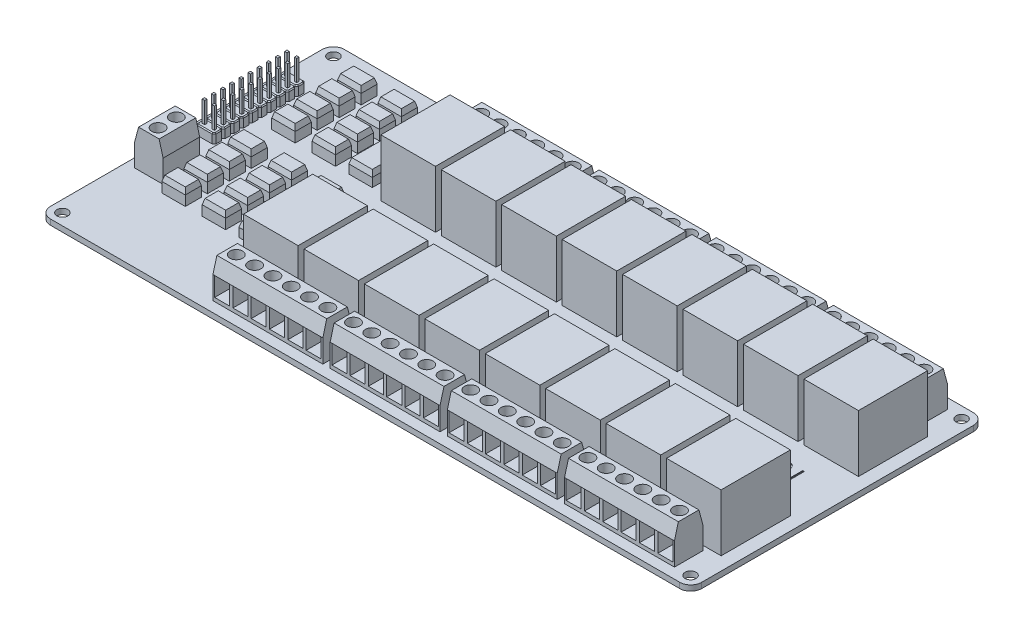
SolidWorks part; units mm, degrees
material "1060 Alloy"
ref_plane "Front" through (0, 0, 0) normal (0, 0, 1) x (1, 0, 0)
ref_plane "Top" through (0, 0, 0) normal (0, 1, 0) x (1, 0, 0)
ref_plane "Right" through (0, 0, 0) normal (1, 0, 0) x (0, 0, -1)
sketch "Sketch1" plane through (0, 0, 0) normal (0, 1, 0) x (1, 0, 0)
  line L1 (-88.9, 40.1) -> (88.9, 40.1)
  line L2 (-88.9, 40.1) -> (-88.9, -40.1)
  line L3 (-88.9, -40.1) -> (88.9, -40.1)
  line L4 (88.9, 40.1) -> (88.9, -40.1)
  line L5 (0, -40.1) -> (0, 40.1) construction
  line L6 (-88.9, 0) -> (88.9, 0) construction
  point P0 (0, 0)
  dimension "D1" = 80.2
  dimension "D2" = 177.8
extrude "Boss-Extrude1" add sketch "Sketch1" along normal blind 1.5
sketch "Sketch2" plane through (0, 1.5, 0) normal (0, 1, 0) x (1, 0, 0)
  line L0 (88.9, -40.1) -> (88.9, 40.1) construction
  line L1 (-85.75, 37) -> (85.75, 37) construction
  line L2 (-85.75, 37) -> (-85.75, -37) construction
  line L3 (-85.75, -37) -> (85.75, -37) construction
  line L4 (85.75, 37) -> (85.75, -37) construction
  line L5 (0, -37) -> (0, 37) construction
  line L6 (-85.75, 0) -> (85.75, 0) construction
  line L7 (88.9, 40.1) -> (-88.9, 40.1) construction
  circle A0 centre (85.75, 37) radius 1.5
  circle A1 centre (85.75, -37) radius 1.5
  circle A2 centre (-85.75, -37) radius 1.5
  circle A3 centre (-85.75, 37) radius 1.5
  point P0 (0, 0)
  point P8 (87.25, 37)
  point P9 (85.75, 38.5)
  dimension "D1" = 3
  dimension "D2" = 1.65
  dimension "D3" = 1.6
  dimension "D4" = 74
  dimension "D5" = 171.5
extrude "Cut-Extrude1" cut sketch "Sketch2" against normal blind 1.5
sketch "Sketch3" plane through (0, 1.5, 0) normal (0, 1, 0) x (1, 0, 0)
  line L0 (88.9, 40.1) -> (-88.9, 40.1) construction
  line L1 (-86.05, 24.7) -> (-81.05, 24.7)
  line L2 (-86.05, 24.7) -> (-86.05, 22.2)
  line L3 (-86.05, 22.2) -> (-81.05, 22.2)
  line L4 (-81.05, 24.7) -> (-81.05, 22.2)
  line L5 (-88.9, 40.1) -> (-88.9, -40.1) construction
  dimension "D1" = 5
  dimension "D2" = 2.5
  dimension "D3" = 15.4
  dimension "D4" = 2.85
extrude "Boss-Extrude2" add sketch "Sketch3" along normal blind 2.6 separate body
sketch "Sketch4" plane through (0, 4.1, 0) normal (0, 1, 0) x (1, 0, 0)
  line L0 (-83.55, 24.7) -> (-83.55, 22.2) construction
  line L1 (-81.05, 24.7) -> (-86.05, 24.7) construction
  line L2 (-86.05, 22.2) -> (-81.05, 22.2) construction
  line L3 (-83.55, 23.45) -> (-82.225, 23.45) construction
  line L4 (-83.55, 23.45) -> (-84.875, 23.45) construction
  line L6 (-82.55, 23.775) -> (-81.9, 23.775)
  line L7 (-82.55, 23.775) -> (-82.55, 23.125)
  line L8 (-82.55, 23.125) -> (-81.9, 23.125)
  line L9 (-81.9, 23.775) -> (-81.9, 23.125)
  line L10 (-82.225, 23.125) -> (-82.225, 23.775) construction
  line L11 (-82.55, 23.45) -> (-81.9, 23.45) construction
  line L12 (-85.2, 23.775) -> (-84.55, 23.775)
  line L13 (-85.2, 23.775) -> (-85.2, 23.125)
  line L14 (-85.2, 23.125) -> (-84.55, 23.125)
  line L15 (-84.55, 23.775) -> (-84.55, 23.125)
  line L16 (-84.875, 23.125) -> (-84.875, 23.775) construction
  line L17 (-85.2, 23.45) -> (-84.55, 23.45) construction
  dimension "D1" = 0.65
  dimension "D2" = 2
  dimension "D3" = 2.65
extrude "Boss-Extrude3" add sketch "Sketch4" along normal blind 5.75 and the other way blind 1.5 separate body
sketch "Sketch5" plane through (-84.55, 0, 0) normal (1, 0, 0) x (0, 0, -1)
  line L0 (23.125, 2.6) -> (23.125, 9.85) construction
  line L1 (23.775, 2.6) -> (23.125, 2.6)
  line L2 (23.775, 2.6) -> (23.775, 3.25)
  line L3 (23.775, 3.25) -> (23.125, 3.25)
  line L4 (23.125, 2.6) -> (23.125, 3.25)
extrude "Boss-Extrude4" add sketch "Sketch5" along normal blind 2
chamfer "Chamfer1" distance 0.5 angle 45 4 edges at (-81.05, 2.8, -24.7) (-81.05, 2.8, -22.2) (-86.05, 2.8, -24.7) (-86.05, 2.8, -22.2)
chamfer "Chamfer2" distance 0.25 angle 45 8 edges at (-81.3, 4.1, -22.45) (-83.55, 4.1, -22.2) (-85.8, 4.1, -22.45) (-86.05, 4.1, -23.45) (-85.8, 4.1, -24.45) (-83.55, 4.1, -24.7) (-81.3, 4.1, -24.45) (-81.05, 4.1, -23.45)
pattern_linear "LPattern1" count 10 spacing 2.5 along (0, 0, 1) of bodies 103 106
sketch "Sketch7" plane through (0, 1.5, 0) normal (0, 1, 0) x (1, 0, 0)
  line L0 (88.9, 40.1) -> (-88.9, 40.1) construction
  line L1 (-76.85, 33.65) -> (-70.45, 33.65)
  line L2 (-76.85, 33.65) -> (-76.85, 29.25)
  line L3 (-76.85, 29.25) -> (-70.45, 29.25)
  line L4 (-70.45, 33.65) -> (-70.45, 29.25)
  line L5 (-88.9, 40.1) -> (-88.9, -40.1) construction
  dimension "D1" = 6.4
  dimension "D2" = 4.4
  dimension "D3" = 6.45
  dimension "D4" = 12.05
extrude "Boss-Extrude6" add sketch "Sketch7" along normal blind 4.23 separate body
chamfer "Chamfer3" distance 1.5 angle 15 4 edges at (-73.65, 5.73, -33.65) (-70.45, 5.73, -31.45) (-73.65, 5.73, -29.25) (-76.85, 5.73, -31.45) first distance on face at (-73.65, 3.615, -33.65) first distance on face at (-70.45, 3.615, -31.45) first distance on face at (-73.65, 3.615, -29.25) first distance on face at (-76.85, 3.615, -31.45)
pattern_linear "LPattern2" count 4 spacing 6 along (0, 0, 1) of bodies 128
pattern_linear "LPattern3" count 2 spacing 30 along (0, 0, 1) count 2 spacing 11 along (1, 0, 0) of bodies 131 130 129 128
sketch "Sketch8" plane through (0, 1.5, 0) normal (0, 1, 0) x (1, 0, 0)
  line L0 (-70.45, 33.65) -> (-76.85, 33.65) construction
  line L1 (-55.8, 33.65) -> (-49.4, 33.65)
  line L2 (-55.8, 33.65) -> (-55.8, 11.25)
  line L3 (-55.8, 11.25) -> (-49.4, 11.25)
  line L4 (-49.4, 33.65) -> (-49.4, 11.25)
  line L5 (-55.8, 3.65) -> (-49.4, 3.65)
  line L6 (-55.8, 3.65) -> (-55.8, -18.75)
  line L7 (-55.8, -18.75) -> (-49.4, -18.75)
  line L8 (-49.4, 3.65) -> (-49.4, -18.75)
  line L9 (-76.85, 11.25) -> (-70.45, 11.25) construction
  line L10 (-59.45, 33.65) -> (-59.45, 29.25) construction
  line L11 (-70.45, 3.65) -> (-76.85, 3.65) construction
  dimension "D1" = 3.65
extrude "Boss-Extrude7" add sketch "Sketch8" along normal blind 3.9 separate body
chamfer "Chamfer4" distance 1.5 angle 15 4 edges at (-52.6, 5.4, -33.65) (-49.4, 5.4, -22.45) (-52.6, 5.4, -11.25) (-55.8, 5.4, -22.45) first distance on face at (-52.6, 3.45, -33.65) first distance on face at (-49.4, 3.45, -22.45) first distance on face at (-52.6, 3.45, -11.25) first distance on face at (-55.8, 3.45, -22.45)
chamfer "Chamfer5" distance 1.5 angle 15 4 edges at (-52.6, 5.4, -3.65) (-49.4, 5.4, 7.55) (-52.6, 5.4, 18.75) (-55.8, 5.4, 7.55) first distance on face at (-52.6, 3.45, -3.65) first distance on face at (-49.4, 3.45, 7.55) first distance on face at (-52.6, 3.45, 18.75) first distance on face at (-55.8, 3.45, 7.55)
sketch "Sketch9" plane through (0, 1.5, 0) normal (0, 1, 0) x (1, 0, 0)
  line L0 (-88.9, 40.1) -> (-88.9, -40.1) construction
  line L1 (-45.1, 28.2) -> (-30.2, 28.2)
  line L2 (-45.1, 28.2) -> (-45.1, 9.3)
  line L3 (-45.1, 9.3) -> (-30.2, 9.3)
  line L4 (-30.2, 28.2) -> (-30.2, 9.3)
  line L5 (88.9, 40.1) -> (-88.9, 40.1) construction
  dimension "D1" = 14.9
  dimension "D2" = 18.9
  dimension "D3" = 43.8
  dimension "D4" = 11.9
extrude "Boss-Extrude8" add sketch "Sketch9" along normal blind 15.6 separate body
pattern_linear "LPattern4" count 8 spacing 16.5 along (1, 0, 0) of bodies 162
mirror "Mirror1" about plane through (0, 0, 0) normal (0, 0, 1) of bodies 163 164 162 165 166 167 168 169
sketch "Sketch10" plane through (0, 1.5, 0) normal (0, 1, 0) x (1, 0, 0)
  line L0 (-88.9, 40.1) -> (-88.9, -40.1) construction
  line L1 (-86.47, -6.55) -> (-78.72, -6.55)
  line L2 (-86.47, -6.55) -> (-86.47, -16.55)
  line L3 (-86.47, -16.55) -> (-78.72, -16.55)
  line L4 (-78.72, -6.55) -> (-78.72, -16.55)
  line L5 (-88.9, -40.1) -> (88.9, -40.1) construction
  dimension "D1" = 10
  dimension "D2" = 7.75
  dimension "D3" = 2.43
  dimension "D4" = 23.55
extrude "Boss-Extrude9" add sketch "Sketch10" along normal blind 10.2 separate body
chamfer "Chamfer6" distance 4 angle 15 2 edges at (-78.72, 11.7, 11.55) (-86.47, 11.7, 11.55) first distance on face at (-78.72, 6.6, 11.55) first distance on face at (-86.47, 6.6, 11.55)
sketch "Sketch11" plane through (0, 11.7, 0) normal (0, 1, 0) x (1, 0, 0)
  line L0 (-82.595, -6.55) -> (-82.595, -9.05) construction
  line L1 (-79.7918, -6.55) -> (-85.3982, -6.55) construction
  line L2 (-85.3982, -11.55) -> (-79.7918, -11.55) construction
  line L3 (-85.3982, -6.55) -> (-85.3982, -16.55) construction
  line L4 (-79.7918, -16.55) -> (-79.7918, -6.55) construction
  line L5 (-82.595, -9.05) -> (-82.595, -11.55) construction
  line L6 (-82.595, -11.55) -> (-82.595, -14.05) construction
  line L7 (-82.595, -14.05) -> (-82.595, -16.55) construction
  line L8 (-85.3982, -16.55) -> (-79.7918, -16.55) construction
  circle A0 centre (-82.595, -9.05) radius 1.725
  circle A1 centre (-82.595, -14.05) radius 1.725
  dimension "D1" = 3.45
  dimension "D2" = 5
extrude "Cut-Extrude2" cut sketch "Sketch11" against normal blind 5
sketch "Sketch12" plane through (-86.47, 0, 0) normal (-1, 0, 0) x (0, 0, 1)
  line L0 (11.55, 7.7) -> (11.55, 1.5) construction
  line L1 (7, 7.7) -> (11.1, 7.7)
  line L2 (7, 7.7) -> (7, 2.5)
  line L3 (7, 2.5) -> (11.1, 2.5)
  line L4 (11.1, 7.7) -> (11.1, 2.5)
  line L5 (12, 7.7) -> (16.1, 7.7)
  line L6 (12, 7.7) -> (12, 2.5)
  line L7 (12, 2.5) -> (16.1, 2.5)
  line L8 (16.1, 7.7) -> (16.1, 2.5)
  line L9 (16.55, 7.7) -> (6.55, 7.7) construction
  line L10 (6.55, 1.5) -> (16.55, 1.5) construction
  line L11 (16.55, 7.7) -> (16.55, 1.5) construction
  line L12 (14.05, 7.7) -> (14.05, 2.5) construction
  line L13 (9.05, 7.7) -> (9.05, 2.5) construction
  dimension "D1" = 0.45
  dimension "D2" = 0.9
  dimension "D3" = 5
  dimension "D4" = 1
extrude "Cut-Extrude3" cut sketch "Sketch12" against normal blind 7
sketch "Sketch14" plane through (0, 1.5, 0) normal (0, 1, 0) x (1, 0, 0)
  line L0 (-30.2, -18.75) -> (-28.6, -18.75) construction
  line L1 (-44.4, -29.5) -> (-14.4, -29.5)
  line L2 (-44.4, -29.5) -> (-44.4, -37.25)
  line L3 (-44.4, -37.25) -> (-14.4, -37.25)
  line L4 (-14.4, -29.5) -> (-14.4, -37.25)
  line L6 (-30.2, -9.3) -> (-30.2, -28.2) construction
  line L7 (-28.6, -28.2) -> (-28.6, -9.3) construction
  line L8 (-29.4, -18.75) -> (-29.4, -29.5) construction
  line L9 (-88.9, -40.1) -> (88.9, -40.1) construction
  dimension "D1" = 7.75
  dimension "D2" = 30
  dimension "D3" = 2.85
extrude "Boss-Extrude10" add sketch "Sketch14" along normal blind 10.2 separate body
chamfer "Chamfer7" distance 4 angle 15 2 edges at (-29.4, 11.7, 29.5) (-29.4, 11.7, 37.25) first distance on face at (-29.4, 6.6, 29.5) first distance on face at (-29.4, 6.6, 37.25)
sketch "Sketch15" plane through (0, 11.7, 0) normal (0, 1, 0) x (1, 0, 0)
  line L0 (-29.4, -30.5718) -> (-29.4, -36.1782) construction
  line L3 (-14.4, -30.5718) -> (-44.4, -30.5718) construction
  line L4 (-44.4, -36.1782) -> (-14.4, -36.1782) construction
  line L5 (-31.9, -33.375) -> (-29.4, -33.375) construction
  circle A0 centre (-31.9, -33.375) radius 1.725
  circle A1 centre (-36.9, -33.375) radius 1.725
  circle A2 centre (-41.9, -33.375) radius 1.725
  circle A3 centre (-16.9, -33.375) radius 1.725
  circle A4 centre (-21.9, -33.375) radius 1.725
  circle A5 centre (-26.9, -33.375) radius 1.725
  dimension "D1" = 3.45
  dimension "D2" = 2.5
  dimension "D4" = 5
  dimension "D3" = 3
extrude "Cut-Extrude4" cut sketch "Sketch15" against normal blind 5
sketch "Sketch16" plane through (0, 0, 37.25) normal (0, 0, 1) x (1, 0, 0)
  line L0 (-44.4, 7.7) -> (-44.4, 1.5) construction
  line L1 (-43.95, 7.7) -> (-39.85, 7.7)
  line L2 (-43.95, 7.7) -> (-43.95, 2.5)
  line L3 (-43.95, 2.5) -> (-39.85, 2.5)
  line L4 (-39.85, 7.7) -> (-39.85, 2.5)
  line L5 (-14.4, 7.7) -> (-44.4, 7.7) construction
  line L6 (-44.4, 1.5) -> (-14.4, 1.5) construction
  dimension "D1" = 0.45
  dimension "D2" = 1
  dimension "D3" = 4.1
extrude "Cut-Extrude5" cut sketch "Sketch16" against normal blind 7
pattern_linear "LPattern5" count 6 spacing 5 along (1, 0, 0) of "Cut-Extrude5"
pattern_linear "LPattern6" count 4 spacing 32 along (1, 0, 0) of bodies 184
mirror "Mirror2" about plane through (0, 0, 0) normal (0, 0, 1) of bodies 184 185 186 187
fillet "Fillet1" radius 3 4 edges at (-88.9, 0.75, -40.1) (-88.9, 0.75, 40.1) (88.9, 0.75, -40.1) (88.9, 0.75, 40.1)
sketch "Sketch17" plane through (0, 1.5, 0) normal (0, 1, 0) x (1, 0, 0)
  line L0 (78.4543, 3.1193) -> (-42.7245, 3.1193) construction
  text T0 "16 Relay Module   Low Level Trigger" font "Century Gothic" height 5
extrude "Cut-Extrude6" cut sketch "Sketch17" against normal blind 0.25
